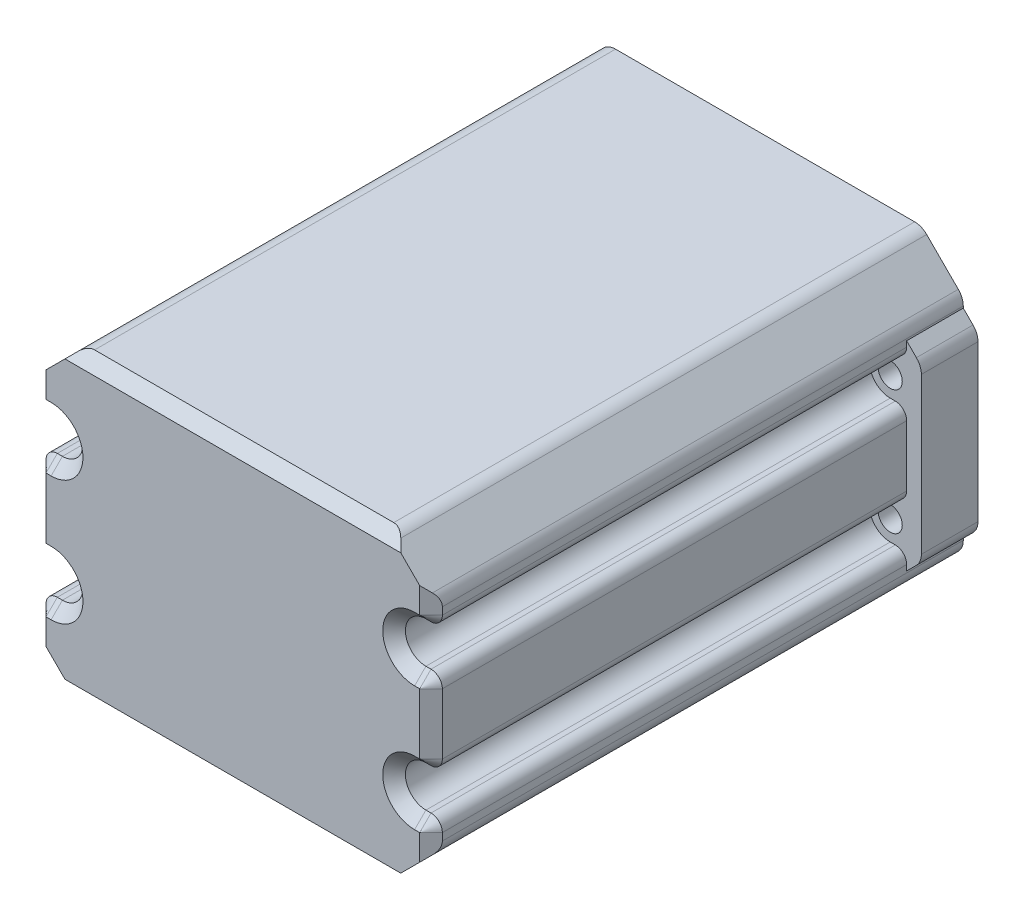
SolidWorks part; units mm, degrees
note: The reader was unsure of these and kept them because the rebuilt part matched: shared geometry of "Sketch1<3>".
ref_plane "Front Plane" through (0, 0, 0) normal (0, 0, 1) x (1, 0, 0)
ref_plane "Top Plane" through (0, 0, 0) normal (0, 1, 0) x (1, 0, 0)
ref_plane "Right Plane" through (0, 0, 0) normal (1, 0, 0) x (0, 0, -1)
sketch "Sketch1" plane through (0, 0, 0) normal (0, 0, 1) x (1, 0, 0)
  line L0 (27.6569, 53) -> (27.6569, 0) construction
  line L2 (-3.3431, 9.6017) -> (-3.3431, 9)
  line L4 (-4.4431, 41.125) -> (-7.3431, 41.125)
  line L5 (-4.4431, 33.875) -> (-7.3431, 33.875)
  line L6 (-4.4431, 11.875) -> (-7.3431, 11.875)
  line L7 (-4.4431, 19.125) -> (-7.3431, 19.125)
  line L8 (-7.3431, 41.5) -> (-9.9431, 41.5)
  line L13 (-9.9431, 41.5) -> (-9.9431, 11.5)
  line L17 (55.3137, 53) -> (0, 53)
  line L18 (0, 53) -> (-7.3431, 45.6569)
  line L19 (-7.3431, 45.6569) -> (-7.3431, 41.125)
  line L20 (-7.3431, 7.3431) -> (0, 0)
  line L21 (0, 0) -> (55.3137, 0)
  line L28 (-7.3431, 11.875) -> (-7.3431, 7.3431)
  line L29 (-7.3431, 33.875) -> (-7.3431, 19.125)
  line L30 (-7.3431, 33.875) -> (-7.3431, 19.125)
  line L33 (27.6569, 49) -> (1.6569, 49)
  line L37 (1.6569, 4) -> (27.6569, 4)
  line L38 (-3.3431, 9) -> (1.6569, 4)
  line L44 (1.5569, 37.5) -> (1.5569, 15.5)
  line L46 (1.6569, 49) -> (-3.3431, 44)
  line L47 (-3.3431, 44) -> (-3.3431, 43.3983)
  line L50 (-9.9431, 11.5) -> (-7.3431, 11.5)
  line L57 (65.2569, 11.5) -> (62.6569, 11.5)
  line L58 (58.6569, 44) -> (58.6569, 43.3983)
  line L59 (53.6569, 49) -> (58.6569, 44)
  line L60 (53.7569, 37.5) -> (53.7569, 15.5)
  line L61 (58.6569, 9) -> (53.6569, 4)
  line L62 (53.6569, 4) -> (27.6569, 4)
  line L63 (27.6569, 49) -> (53.6569, 49)
  line L64 (62.6569, 33.875) -> (62.6569, 19.125)
  line L66 (62.6569, 33.875) -> (62.6569, 19.125)
  line L67 (62.6569, 11.875) -> (62.6569, 7.3431)
  line L68 (62.6569, 7.3431) -> (55.3137, 0)
  line L70 (62.6569, 45.6569) -> (62.6569, 41.125)
  line L71 (55.3137, 53) -> (62.6569, 45.6569)
  line L72 (65.2569, 41.5) -> (65.2569, 11.5)
  line L73 (62.6569, 41.5) -> (65.2569, 41.5)
  line L74 (59.7569, 19.125) -> (62.6569, 19.125)
  line L75 (59.7569, 11.875) -> (62.6569, 11.875)
  line L76 (59.7569, 33.875) -> (62.6569, 33.875)
  line L77 (59.7569, 41.125) -> (62.6569, 41.125)
  line L78 (58.6569, 9.6017) -> (58.6569, 9)
  line L79 (-9.9431, 41.5) -> (-9.9431, 11.5) construction
  line L80 (-9.9431, 41.5) -> (-7.3431, 44.1)
  line L81 (-9.9431, 11.5) -> (-7.3431, 8.9)
  line L82 (-7.3431, 8.9) -> (-7.3431, 11.5)
  line L83 (-7.3431, 44.1) -> (-7.3431, 41.5)
  line L84 (62.6569, 41.5) -> (65.2569, 41.5)
  line L85 (65.2569, 41.5) -> (62.6569, 44.1)
  line L86 (65.2569, 41.5) -> (62.6569, 44.1) construction
  line L87 (62.6569, 44.1) -> (62.6569, 41.5)
  line L88 (65.2569, 11.5) -> (62.6569, 8.9)
  line L89 (62.6569, 8.9) -> (65.2569, 11.5) construction
  line L90 (62.6569, 8.9) -> (62.6569, 11.5)
  arc A0 (-4.4431, 33.875) -> (-4.4431, 41.125) centre (-4.4431, 37.5) ccw
  circle A1 centre (-4.4431, 15.5) radius 2.125
  circle A4 centre (-4.4431, 37.5) radius 2.125
  arc A5 (-4.4431, 11.875) -> (-4.4431, 19.125) centre (-4.4431, 15.5) ccw
  arc A14 (58.6569, 9.6017) -> (53.7569, 15.5) centre (59.7569, 15.5) cw
  arc A26 (1.5569, 37.5) -> (-3.3431, 43.3983) centre (-4.4431, 37.5) ccw
  arc A27 (-3.3431, 9.6017) -> (1.5569, 15.5) centre (-4.4431, 15.5) ccw
  arc A28 (53.7569, 37.5) -> (58.6569, 43.3983) centre (59.7569, 37.5) cw
  arc A29 (59.7569, 11.875) -> (59.7569, 19.125) centre (59.7569, 15.5) cw
  circle A30 centre (59.7569, 37.5) radius 2.125
  circle A31 centre (59.7569, 15.5) radius 2.125
  arc A32 (59.7569, 33.875) -> (59.7569, 41.125) centre (59.7569, 37.5) cw
  point P43 (14.6569, 4)
  point P44 (14.6569, 49)
  point P63 (40.6569, 49)
  point P64 (40.6569, 4)
  point P75 (1.5569, 26.5)
  point P76 (27.6569, 26.5)
  dimension "D3" = 7.25
  dimension "D4" = 4.25
  dimension "D5" = 12
  dimension "D6" = 22
  dimension "D7" = 32.1
  dimension "D1" = 45
  dimension "D2" = 45
  dimension "D8" = 4
  dimension "D9" = 45
  dimension "D10" = 5
  dimension "D11" = 4
  dimension "D12" = 4
  dimension "D13" = 4
  dimension "D14" = 5
  dimension "D15" = 4
  dimension "D16" = 31
extrude "Boss-Extrude1" add sketch "Sketch1" along normal blind 90
extrude "Boss-Extrude2" add sketch "Sketch1<3>" along normal blind 10
sketch "Sketch1<3>" plane through (0, 0, 0) normal (0, 0, 1) x (1, 0, 0) same geometry as "Sketch1"
fillet "Fillet1" radius 2 8 edges at (-7.3431, 41.125, 50) (-7.3431, 19.125, 50) (-7.3431, 11.875, 50) (-7.3431, 33.875, 50) (62.6569, 41.125, 50) (62.6569, 33.875, 50) (62.6569, 19.125, 50) (62.6569, 11.875, 50)
sketch "Sketch2" plane through (0, 0, 90) normal (0, 0, 1) x (1, 0, 0)
  line L21 (-7.3431, 31.875) -> (-7.3431, 21.125)
  line L28 (-7.3431, 9.875) -> (-7.3431, 7.3431)
  line L37 (55.3137, 0) -> (62.6569, 7.3431)
  line L43 (55.3137, 53) -> (0, 53)
  line L44 (0, 53) -> (-7.3431, 45.6569)
  line L45 (-7.3431, 45.6569) -> (-7.3431, 43.125)
  line L46 (-5.3431, 41.125) -> (-4.4431, 41.125)
  line L47 (-4.4431, 33.875) -> (-5.3431, 33.875)
  line L49 (-5.3431, 19.125) -> (-4.4431, 19.125)
  line L50 (-4.4431, 11.875) -> (-5.3431, 11.875)
  line L52 (-7.3431, 7.3431) -> (0, 0)
  line L53 (0, 0) -> (55.3137, 0)
  line L72 (62.6569, 7.3431) -> (62.6569, 9.875)
  line L82 (60.6569, 11.875) -> (59.7569, 11.875)
  line L86 (59.7569, 19.125) -> (60.6569, 19.125)
  line L90 (62.6569, 21.125) -> (62.6569, 31.875)
  line L92 (60.6569, 33.875) -> (59.7569, 33.875)
  line L94 (59.7569, 41.125) -> (60.6569, 41.125)
  line L96 (62.6569, 43.125) -> (62.6569, 45.6569)
  line L98 (62.6569, 45.6569) -> (55.3137, 53)
  arc A12 (59.7569, 19.125) -> (59.7569, 11.875) centre (59.7569, 15.5) ccw
  arc A15 (59.7569, 41.125) -> (59.7569, 33.875) centre (59.7569, 37.5) ccw
  arc A18 (-7.3431, 43.125) -> (-5.3431, 41.125) centre (-5.3431, 43.125) ccw
  arc A23 (-5.3431, 33.875) -> (-7.3431, 31.875) centre (-5.3431, 31.875) ccw
  arc A31 (-7.3431, 21.125) -> (-5.3431, 19.125) centre (-5.3431, 21.125) ccw
  arc A35 (-5.3431, 11.875) -> (-7.3431, 9.875) centre (-5.3431, 9.875) ccw
  arc A46 (-4.4431, 33.875) -> (-4.4431, 41.125) centre (-4.4431, 37.5) ccw
  arc A49 (-4.4431, 11.875) -> (-4.4431, 19.125) centre (-4.4431, 15.5) ccw
  arc A62 (60.6569, 41.125) -> (62.6569, 43.125) centre (60.6569, 43.125) ccw
  arc A64 (62.6569, 9.875) -> (60.6569, 11.875) centre (60.6569, 9.875) ccw
  arc A66 (60.6569, 19.125) -> (62.6569, 21.125) centre (60.6569, 21.125) ccw
  arc A68 (62.6569, 31.875) -> (60.6569, 33.875) centre (60.6569, 31.875) ccw
extrude "Boss-Extrude3" add sketch "Sketch2" along normal blind 4
chamfer "Chamfer1" distance 2 angle 45 28 edges at (27.6569, 0, 94) (27.6569, 53, 94) (-4.8931, 11.875, 94) (-0.8181, 15.5, 94) (-4.8931, 19.125, 94) (-7.3431, 44.3909, 94) (-6.7574, 41.7108, 94) (-4.8931, 41.125, 94) (-4.8931, 33.875, 94) (-0.8181, 37.5, 94) (-7.3431, 8.6091, 94) (-6.7574, 11.2892, 94) (-6.7574, 19.7108, 94) (-7.3431, 26.5, 94) (-6.7574, 33.2892, 94) (62.6569, 8.6091, 94) (62.6569, 44.3909, 94) (62.0711, 11.2892, 94) (62.0711, 41.7108, 94) (60.2069, 11.875, 94) (60.2069, 41.125, 94) (56.1319, 15.5, 94) (56.1319, 37.5, 94) (60.2069, 19.125, 94) (60.2069, 33.875, 94) (62.0711, 19.7108, 94) (62.0711, 33.2892, 94) (62.6569, 26.5, 94)
fillet "Fillet3" radius 3 12 edges at (-9.9431, 11.5, 5) (65.2569, 11.5, 5) (65.2569, 41.5, 5) (62.6569, 45.6569, 46) (55.3137, 53, 46) (0, 53, 46) (-7.3431, 45.6569, 46) (-9.9431, 41.5, 5) (55.3137, 0, 46) (62.6569, 7.3431, 46) (0, 0, 46) (-7.3431, 7.3431, 46)
